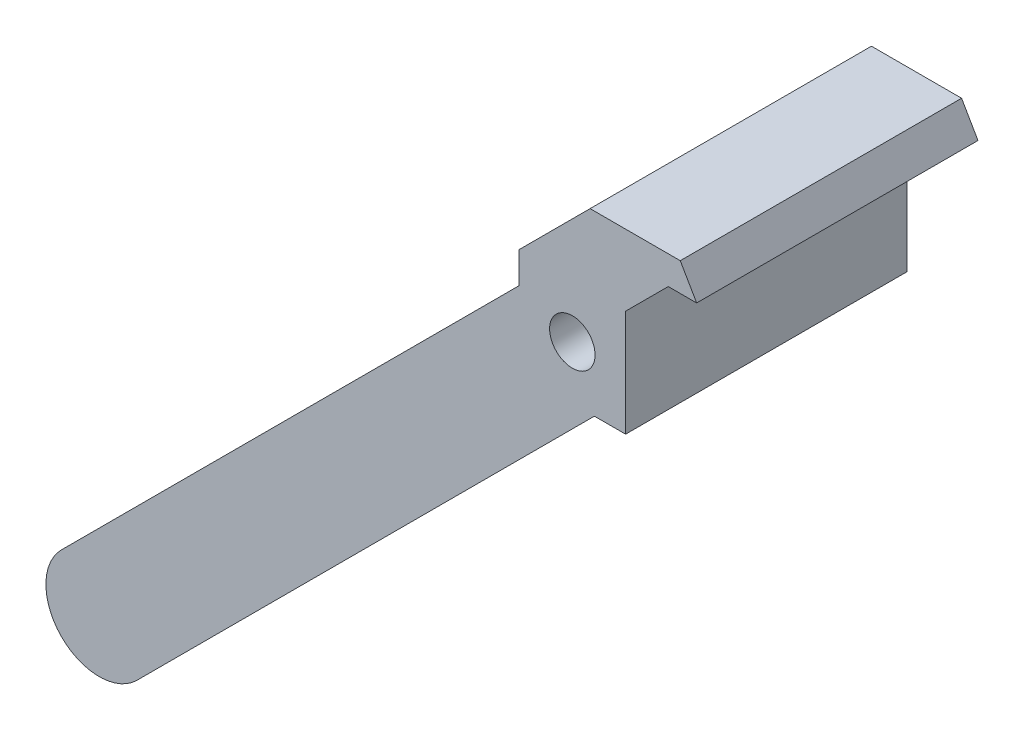
SolidWorks part; units mm, degrees
ref_plane "Front Plane" through (0, 0, 0) normal (0, 0, 1) x (1, 0, 0)
ref_plane "Top Plane" through (0, 0, 0) normal (0, 1, 0) x (1, 0, 0)
ref_plane "Right Plane" through (0, 0, 0) normal (1, 0, 0) x (0, 0, -1)
sketch "Sketch1" plane through (0, 0, 0) normal (0, 0, 1) x (1, 0, 0)
  line L1 (-3.75, -3.75) -> (3.75, -3.75)
  line L2 (-3.75, -3.75) -> (-3.75, 3.75)
  line L3 (-3.75, 3.75) -> (3.75, 3.75)
  line L4 (3.75, -3.75) -> (3.75, 3.75)
  line L5 (-3.75, -3.75) -> (3.75, 3.75) construction
  line L6 (-3.75, 3.75) -> (3.75, -3.75) construction
  circle A0 centre (0, 0) radius 1.6
  point P0 (0, 0)
  dimension "D3" = 3.2
  dimension "D1" = 7.5
  dimension "D2" = 7.5
extrude "Boss-Extrude1" add sketch "Sketch1" along normal blind 9.9 and the other way blind 9.9
sketch "Sketch2" plane through (0, 0, 9.9) normal (0, 0, 1) x (1, 0, 0)
  line L0 (3.75, 3.75) -> (6.75, 6.75)
  line L1 (6.75, 6.75) -> (8.75, 6.75)
  line L2 (8.75, 6.75) -> (7.5953, 8.75)
  line L3 (7.5953, 8.75) -> (1.25, 8.75)
  line L4 (1.25, 8.75) -> (-3.75, 3.75)
  line L6 (3.75, 3.75) -> (-3.75, 3.75) construction
  line L7 (3.75, 3.75) -> (-3.75, 3.75)
  dimension "D1" = 60
  dimension "D2" = 2
  dimension "D3" = 3
  dimension "D4" = 45
  dimension "D5" = 2
extrude "Boss-Extrude2" add sketch "Sketch2" against normal up to surface (19.8 mm away) contours L4 L7 L0 L1 L2 L3 up to face at (1.6, 0, -9.9)
sketch "Sketch3" plane through (0, 0, 9.9) normal (0, 0, 1) x (1, 0, 0)
  line L0 (0, 0) -> (-33.2985, -33.2985) construction
  line L1 (2.6517, -2.6517) -> (-30.6469, -35.9502)
  line L2 (-2.6517, 2.6517) -> (-35.9502, -30.6469)
  line L3 (3.75, -3.75) -> (3.75, 3.75) construction
  arc A0 (2.6517, -2.6517) -> (-2.6517, 2.6517) centre (0, 0) ccw
  arc A1 (-35.9502, -30.6469) -> (-30.6469, -35.9502) centre (-33.2985, -33.2985) ccw
  circle A2 centre (0, 0) radius 1.6 construction
  circle A3 centre (0, 0) radius 1.6
  point P3 (-16.6493, -16.6493)
extrude "Boss-Extrude3" add sketch "Sketch3" against normal up to surface (19.8 mm away) up to face at (1.6, 0, -9.9)
